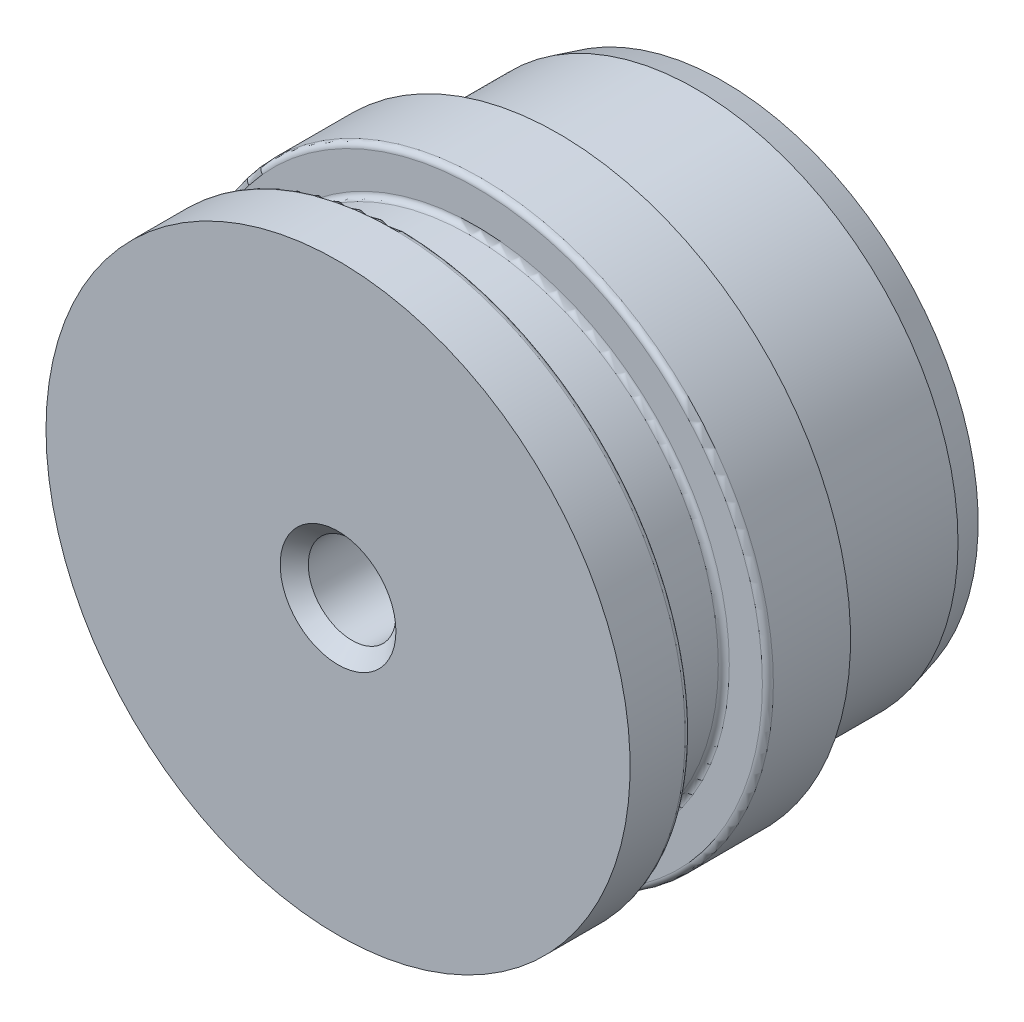
SolidWorks part; units mm, degrees
note: '?' marks a value the reader was unsure of.
ref_plane "Front Plane" through (0, 0, 0) normal (0, 0, 1) x (1, 0, 0)
ref_plane "Top Plane" through (0, 0, 0) normal (0, 1, 0) x (1, 0, 0)
ref_plane "Right Plane" through (0, 0, 0) normal (1, 0, 0) x (0, 0, -1)
ref_axis "Axis2" through (0, 0, -17.6438) along (0, 0, -1)
sketch "Sketch1" plane through (0, 0, 0) normal (1, 0, 0) x (0, 0, -1)
  line L0 (0, 0) -> (0, 13.462)
  line L1 (0, 13.462) -> (2.794, 13.462)
  line L2 (2.794, 13.462) -> (2.794, 11.43)
  line L3 (2.794, 11.43) -> (6.35, 11.43)
  line L4 (6.35, 11.43) -> (6.35, 13.462)
  line L5 (6.35, 13.462) -> (10.16, 13.462)
  line L6 (10.16, 13.462) -> (10.16, 12.065)
  line L7 (17.78, 5.5118) -> (12.192, 5.5118)
  line L8 (12.192, 0) -> (0, 0)
  line L9 (12.192, 5.5118) -> (12.192, 0)
  line L11 (10.16, 12.065) -> (17.78, 12.065)
  line L12 (17.78, 12.065) -> (17.78, 5.5118)
  dimension "D1" = 5.5118
  dimension "D2" = 13.462
  dimension "D3" = 11.43
  dimension "D4" = 3.556
  dimension "D5" = 7.62
  dimension "D6" = 3.81
  dimension "D7" = 5.588
  dimension "D8" = 17.78
  dimension "D9" = 12.065
  dimension "D10" = 2.794
  dimension "D11" = 11.43
revolve "Revolve1" add sketch "Sketch1" angle 360 about L8
hole_wizard "#6-32 Tapped Hole1" positions "Sketch3" profile "Sketch2" tap size "#6-32" standard "Ansi Inch"
sketch "Sketch3" plane through (4.5223, 6.077, -17.78) normal (0, 0, -1) x (-1, 0, 0)
  line L0 (-2.6268, -1.9495) -> (4.5223, -14.332) construction
  line L1 (4.5223, -14.332) -> (11.6713, -1.9495) construction
  line L2 (11.6713, -1.9495) -> (-2.6268, -1.9495) construction
  circle A0 centre (4.5223, -6.077) radius 8.255 construction
  point P0 (-2.6268, -1.9495)
  point P1 (4.5223, -14.332)
  point P3 (11.6713, -1.9495)
  dimension "D1" = 16.51
sketch "Sketch2" plane through (7.149, 4.1275, -17.78) normal (1, 0, 0) x (0, 1, 0)
  line L0 (0, 0) -> (0, 10.2107)
  line L1 (0, 10.2107) -> (1.3525, 9.398)
  line L2 (1.3525, 9.398) -> (1.3525, 0)
  line L5 (1.3525, 0) -> (0, 0)
  line L10 (0, 10.2107) -> (-1.3526, 9.398) construction
  line L11 (0, -6.35) -> (0, 107.95) construction
  dimension "Tap Drill Dia." = 2.7051
  dimension "Tap Drill Depth" = 9.398
  dimension "Drill Angle" = 118
chamfer "Chamfer1" distance 1.27 angle 20 1 edges at (-5.5118, 0, -17.78) first distance on face at (-5.5118, 0, -17.78)
hole_wizard "1/16 (0.0625) Diameter Hole1" [suppressed] positions "Sketch5" profile "Sketch4" hole size "1/16" standard "Ansi Inch"
sketch "Sketch5" plane through (0, 0, 0) normal (0, 0, 1) x (1, 0, 0)
  point P0 (0, 0)
sketch "Sketch4" plane through (0, 0, 0) normal (1, 0, 0) x (0, -1, 0)
  line L0 (0, 0) -> (0, 16.51)
  line L1 (0, 16.51) -> (0.7937, 16.51)
  line L2 (0.7937, 16.51) -> (0.7937, 0)
  line L5 (0.7937, 0) -> (0, 0)
  line L11 (0, -6.35) -> (0, 107.95) construction
  dimension "Thru Hole Dia." = 1.5875
  dimension "Thru Hole Depth" = 16.51
sketch "Sketch6" [suppressed] plane through (0, 0, 0) normal (0, 0, 1) x (1, 0, 0)
  circle A0 centre (0, 0) radius 7.428
extrude "Solidify core" [suppressed] add sketch "Sketch6" against normal through all
sketch "Sketch7" plane through (0, 0, 0) normal (0, 0, 1) x (1, 0, 0)
  line L0 (-11.8703, 6.35) -> (11.8703, 6.35) construction
  circle A0 centre (0, 0) radius 13.462 construction
  dimension "D1" = 6.35
ref_plane "Plane1" through (0, 0.7428, 2.0409) normal (0, 0.342, 0.9397) x (-1, 0, 0)
sketch "Sketch8" plane through (0, 0.7428, 2.0409) normal (0, 0.342, 0.9397) x (-1, 0, 0)
  line L0 (11.8703, -5.967) -> (-11.8703, -5.967) construction
  circle A0 centre (0, -5.967) radius 4.826
  dimension "D1" = 9.652
extrude "Cbore-in" [suppressed] cut sketch "Sketch8" against normal mid plane 2.54
ref_axis "Axis1" [suppressed] through (0, 6.35, 0) along (0, 0.342, 0.9397)?
sketch "Sketch14" plane through (0, 0.7428, 2.0409) normal (0, 0.342, 0.9397) x (-1, 0, 0)
  circle A0 centre (0, -5.967) radius 4.826 construction
  circle A1 centre (0, -5.967) radius 4.826
extrude "Cbore--out" [suppressed] cut sketch "Sketch14" along normal blind 6.35
sketch "Sketch9" [suppressed] plane through (0, 0, 0) normal (1, 0, 0) x (0, 0, -1)
  line L0 (1.1934, 5.9156) -> (9.1893, 3.0054) construction
  line L1 (2.844, 10.4506) -> (0, 2.6368) construction
  line L2 (9.1893, 3.0054) -> (9.4803, 3.805)
  line L3 (9.4803, 3.805) -> (7.8276, 5.1917)
  line L4 (7.8276, 5.1917) -> (7.7318, 5.6848)
  line L5 (7.7318, 5.6848) -> (1.8841, 7.8132)
  line L6 (1.8841, 7.8132) -> (1.1934, 5.9156)
  line L7 (1.1934, 5.9156) -> (9.1893, 3.0054)
  line L8 (7.7318, 5.6848) -> (7.0411, 3.7872) construction
  line L9 (0, 6.35) -> (-3.9506, 7.7879) construction
  line L10 (-0.8255, 0) -> (17.3355, 0) construction
  circle A0 centre (8.151, 3.3833) radius 1.1811 construction
  dimension "D7" = 2.3622
  dimension "D1" = 1.7018
  dimension "D2" = 20
  dimension "D3" = 59
  dimension "D4" = 4.0386
  dimension "D5" = 6.223
  dimension "D6" = 8.509
  dimension "D8" = 20
revolve "Church tap" [suppressed] cut sketch "Sketch9" angle 360 about L7
hole_wizard "1/16 (0.0625) Diameter Hole2" [suppressed] positions "Sketch11" profile "Sketch10" hole size "1/16" standard "Ansi Inch"
sketch "Sketch11" [suppressed] plane through (0, -2.6018, -7.1484) normal (0, 0.342, 0.9397) x (1, 0, 0)
  line L0 (-11.8703, 5.967) -> (11.8703, 5.967) construction
  point P0 (0, 5.967)
sketch "Sketch10" plane through (0, 3.0054, -9.1893) normal (1, 0, 0) x (0, -0.9397, 0.342)
  line L0 (0, 0) -> (0, 5.2396)
  line L1 (0, 5.2396) -> (0.7937, 4.7627)
  line L2 (0.7937, 4.7627) -> (0.7937, 0)
  line L5 (0.7937, 0) -> (0, 0)
  line L10 (0, 5.2396) -> (-0.7938, 4.7627) construction
  line L11 (0, -6.35) -> (0, 107.95) construction
  dimension "Hole Dia." = 1.5875
  dimension "Hole Depth" = 4.7627
  dimension "Drill Angle" = 118
hole_wizard "#10-32 Tapped Hole1" [suppressed] positions "Sketch13" profile "Sketch12" tap size "#10-32" standard "Ansi Inch"
sketch "Sketch13" [suppressed] plane through (0, 0.3084, 0.8474) normal (0, 0.342, 0.9397) x (1, 0, 0)
  point P0 (0, 5.967)
sketch "Sketch12" plane through (0, 5.9156, -1.1934) normal (1, 0, 0) x (0, -0.9397, 0.342)
  line L0 (0, 0) -> (0, 7.4363)
  line L1 (0, 7.4363) -> (2.0193, 6.223)
  line L2 (2.0193, 6.223) -> (2.0193, 0.6477)
  line L3 (2.0193, 0.6477) -> (2.667, 0)
  line L5 (2.667, 0) -> (0, 0)
  line L6 (-2.0193, 0.6477) -> (-2.667, 0) construction
  line L10 (0, 7.4363) -> (-2.0193, 6.223) construction
  line L11 (0, -6.35) -> (0, 107.95) construction
  dimension "Tap Drill Dia." = 4.0386
  dimension "Tap Drill Depth" = 6.223
  dimension "Near C'Sink Dia." = 5.334
  dimension "Near C'Sink Angle" = 90
  dimension "Drill Angle" = 118
sketch "Sketch15" plane through (0, 0, 0) normal (1, 0, 0) x (0, 0, -1)
  line L0 (10.414, 0.508) -> (17.78, 0.508)
  line L1 (8.5323, 0.8509) -> (10.414, 0.8509)
  line L3 (8.5323, 0.8509) -> (6.9628, 1.4221)
  line L4 (6.9628, 1.4221) -> (6.604, 2.0193)
  line L5 (6.604, 2.0193) -> (0, 2.0193)
  line L7 (0, 0) -> (17.78, 0)
  line L8 (0, 13.462) -> (0, -13.462) construction
  line L9 (10.414, 0.8509) -> (10.414, 0.508)
  line L10 (17.78, 0.508) -> (17.78, 0)
  line L11 (17.6438, 0) -> (23.1226, 0) construction
  line L12 (17.78, -12.065) -> (17.78, 12.065) construction
  line L14 (0, 2.0193) -> (0, 0)
  circle A0 centre (7.4168, 0) radius 1.1811 construction
  dimension "D7" = 2.3622
  dimension "D5" = 7.4168
  dimension "D1" = 2.0193
  dimension "D2" = 0.8509
  dimension "D3" = 0.508
  dimension "D4" = 20
  dimension "D6" = 59
  dimension "D8" = 6.604
  dimension "D9" = 10.414
revolve "Church tap on CL" cut sketch "Sketch15" angle 360 about axis through (0, 0, -17.6438) along (0, 0, -1)
hole_wizard "#10-32 Tapped Hole2" positions "Sketch17" profile "Sketch16" tap size "#10-32" standard "Ansi Inch"
sketch "Sketch17" plane through (0, 0, 0) normal (0, 0, 1) x (1, 0, 0)
  point P0 (0, 0)
sketch "Sketch16" plane through (0, 0, 0) normal (1, 0, 0) x (0, -1, 0)
  line L0 (0, 0) -> (0, 7.2077)
  line L1 (0, 7.2077) -> (2.0193, 5.9944)
  line L2 (2.0193, 5.9944) -> (2.0193, 0.6477)
  line L3 (2.0193, 0.6477) -> (2.667, 0)
  line L5 (2.667, 0) -> (0, 0)
  line L6 (-2.0193, 0.6477) -> (-2.667, 0) construction
  line L10 (0, 7.2077) -> (-2.0193, 5.9944) construction
  line L11 (0, -6.35) -> (0, 107.95) construction
  dimension "Tap Drill Dia." = 4.0386
  dimension "Tap Drill Depth" = 5.9944
  dimension "Near C'Sink Dia." = 5.334
  dimension "Near C'Sink Angle" = 90
  dimension "Drill Angle" = 118
fillet "Fillet1" radius 0.254 4 edges at (-11.43, 0, -2.794) (-11.43, 0, -6.35) (-13.462, 0, -6.35) (-13.462, 0, -2.794)
chamfer "Chamfer2" distance 1.27 angle 15 1 edges at (-12.065, 0, -17.78) first distance on face at (-12.065, 0, -10.16)
